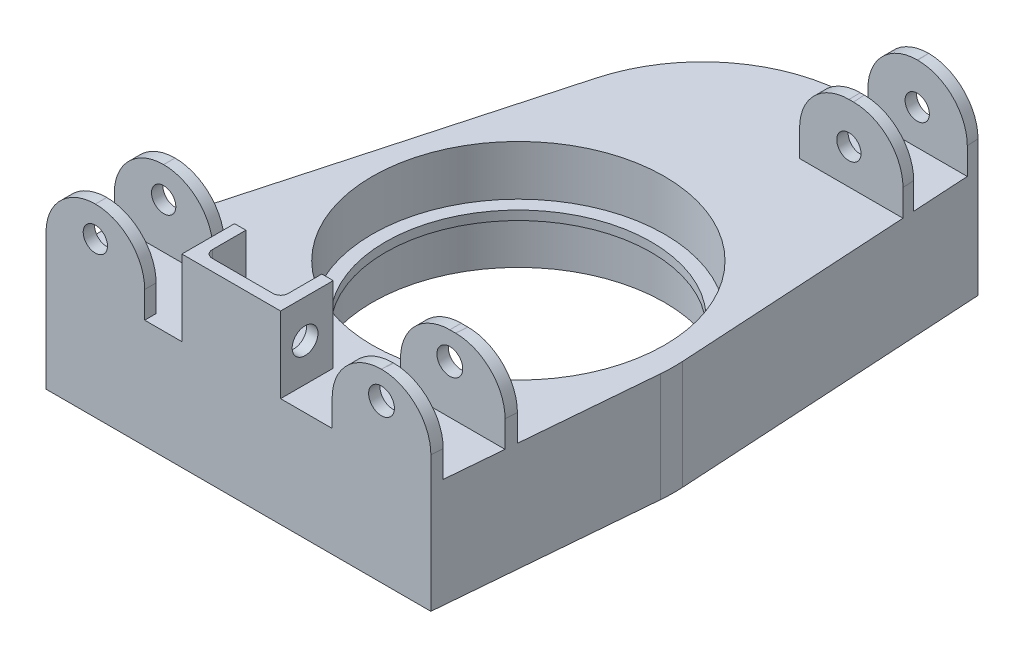
SolidWorks part; units mm, degrees
ref_plane "Front Plane" through (0, 0, 0) normal (0, 0, 1) x (1, 0, 0)
ref_plane "Top Plane" through (0, 0, 0) normal (0, 1, 0) x (1, 0, 0)
ref_plane "Right Plane" through (0, 0, 0) normal (1, 0, 0) x (0, 0, -1)
sketch "Sketch1" plane through (0, 0, 0) normal (0, 1, 0) x (1, 0, 0)
  line L0 (-78.3166, -79.7284) -> (50.4493, -79.7284)
  line L1 (56.8393, -5.2886) -> (50.4493, 103.3395)
  line L2 (50.4493, 103.3395) -> (9.0638, 103.3395)
  line L3 (-39.909, 66.0414) -> (-72.7449, -53.0584)
  line L4 (50.4493, 103.3395) -> (50.4493, -79.7284) construction
  line L5 (50.4493, -79.7284) -> (56.8393, -5.2886)
  line L6 (-78.3166, -79.7284) -> (-78.3166, -53.0584)
  line L7 (-78.3166, -53.0584) -> (-72.7449, -53.0584)
  circle A0 centre (0, 0) radius 48.895
  circle A2 centre (0, 0) radius 120.65
  arc A3 (9.0638, 103.3395) -> (-39.909, 66.0414) centre (9.0638, 52.5395) ccw
  point P10 (0, -48.895)
  point P11 (48.895, 0)
  point P16 (-48.895, 0)
  dimension "D2" = 97.79
  dimension "D3" = 7.62
  dimension "D4" = 8.89
  dimension "D5" = 26.67
  dimension "D1" = 241.3
  dimension "D6" = 50.8
extrude "Base" add sketch "Sketch1" along normal blind 36.5 contours L2 L3 L0 L1 A0 | L1 L4 A0 L5 region at (-76.0411, 0, 66.3934)
sketch "Sketch2" plane through (0, 36.5, 0) normal (0, 1, 0) x (1, 0, 0)
  line L0 (50.4493, 103.3395) -> (50.6734, 99.5295)
  line L1 (56.8393, -5.2886) -> (50.4493, 103.3395) construction
  line L2 (50.6734, 99.5295) -> (17.4293, 99.5295)
  line L3 (17.4293, 99.5295) -> (17.4293, 103.3395)
  line L4 (50.4493, 103.3395) -> (9.0638, 103.3395) construction
  line L5 (17.4293, 103.3395) -> (50.4493, 103.3395)
  line L6 (17.4293, -75.9184) -> (50.7764, -75.9184)
  line L7 (50.7764, -75.9184) -> (50.4493, -79.7284)
  line L8 (-78.3166, -79.7284) -> (50.4493, -79.7284) construction
  line L9 (50.4493, -79.7284) -> (17.4293, -79.7284)
  line L10 (17.4293, -79.7284) -> (17.4293, -75.9184)
  line L11 (17.4293, 103.3395) -> (17.4293, -79.7284) construction
  line L12 (50.4493, -79.7284) -> (56.8393, -5.2886) construction
  line L13 (17.4293, 80.4795) -> (17.4293, 76.6695)
  line L14 (17.4293, 76.6695) -> (52.0182, 76.6695)
  line L15 (52.0182, 76.6695) -> (51.794, 80.4795)
  line L16 (51.794, 80.4795) -> (17.4293, 80.4795)
  line L17 (-78.3166, -79.7284) -> (-78.3166, -53.0584) construction
  line L18 (17.4293, -53.0584) -> (52.7387, -53.0584)
  line L19 (17.4293, -53.0584) -> (17.4293, -56.8684)
  line L20 (17.4293, -56.8684) -> (52.4116, -56.8684)
  line L21 (52.7387, -53.0584) -> (52.4116, -56.8684)
  line L22 (-45.2966, -53.0584) -> (-78.3166, -53.0584)
  line L23 (-45.2966, -53.0584) -> (-45.2966, -56.8684)
  line L24 (-45.2966, -56.8684) -> (-78.3166, -56.8684)
  line L25 (-78.3166, -53.0584) -> (-78.3166, -56.8684)
  line L26 (-45.2966, -79.7284) -> (-45.2966, -60.0458) construction
  line L27 (-78.3166, -75.9184) -> (-45.2966, -75.9184)
  line L28 (-78.3166, -75.9184) -> (-78.3166, -79.7284)
  line L29 (-78.3166, -79.7284) -> (-45.2966, -79.7284)
  line L30 (-45.2966, -75.9184) -> (-45.2966, -79.7284)
  line L31 (-78.3166, -79.7284) -> (50.4493, -79.7284) construction
  dimension "D1" = 33.02
  dimension "D2" = 3.81
  dimension "D3" = 3.81
  dimension "D4" = 19.05
  dimension "D5" = 3.81
  dimension "D6" = 3.81
  dimension "D7" = 19.05
  dimension "D8" = 33.02
  dimension "D9" = 3.81
  dimension "D10" = 3.81
extrude "A-Arms" add sketch "Sketch2" along normal blind 25.4
fillet "Fillet a-arm tab f" radius 16.51 12 edges at (50.6128, 61.9, 77.8234) (52.5752, 61.9, 54.9634) (17.4293, 61.9, 77.8234) (17.4293, 61.9, 54.9634) (51.9061, 61.9, -78.5745) (50.5614, 61.9, -101.4345) (17.4293, 61.9, -78.5745) (17.4293, 61.9, -101.4345) (-78.3166, 61.9, 77.8234) (-45.2966, 61.9, 77.8234) (-45.2966, 61.9, 54.9634) (-78.3166, 61.9, 54.9634)
fillet "Fillet2" radius 50.8 1 edges at (56.8393, 18.25, 5.2886)
ref_plane "Plane1" through (0, 1, 0) normal (0, -1, 0) x (-1, 0, 0)
sketch "Sketch3" plane through (0, 1, 0) normal (0, -1, 0) x (-1, 0, 0)
  line L0 (43.8545, 51.7309) -> (51.7371, 53.9041)
  line L1 (39.909, 66.0414) -> (72.7449, -53.0584) construction
  line L2 (63.9719, -21.2377) -> (72.1885, -18.9724)
  line L3 (54.0145, 33.5988) -> (63.3923, -0.4157)
  line L4 (43.8545, 51.7309) -> (63.9719, -21.2377)
  circle A0 centre (0, 0) radius 71.12
  circle A1 centre (53.7624, 46.5582) radius 4.191
  circle A2 centre (70.1632, -11.6265) radius 4.191
  arc A3 (56.852, 39.5926) -> (51.7371, 53.9041) centre (53.7624, 46.5582) ccw
  arc A4 (72.1885, -18.9724) -> (69.039, -4.0899) centre (70.1632, -11.6265) ccw
  arc A5 (63.3923, -0.4157) -> (69.039, -4.0899) centre (68.2896, 0.9345) ccw
  arc A6 (54.0145, 33.5988) -> (56.852, 39.5926) centre (58.9118, 34.949) cw
  dimension "D1" = 60.452
  dimension "D2" = 142.24
  dimension "D3" = 8.382
  dimension "D4" = 8.382
  dimension "D5" = 15.24
  dimension "D6" = 15.24
  dimension "D7" = 5.08
extrude "Boss-Extrude3" add sketch "Sketch3" against normal blind 10 contours L3 A6 A3 A0 A1 L0 L4 L2 A2 A4 A5 | A0 A3 L0 A1 | L2 A4 A0 A2 region at (-57.0001, 1, -15.6865) region at (-49.7533, 1, -53.1565) region at (-69.0083, 1, 17.9571)
fillet "Fillet3" radius 12.7 2 edges at (-43.8545, 6, -51.7309) (-63.9719, 6, 21.2377)
sketch "Sketch6" plane through (0, 0, -103.3395) normal (0, 0, -1) x (-1, 0, 0)
  line L0 (-33.9251, 61.9) -> (-33.9251, 40.2979) construction
  circle A1 centre (-33.9251, 48.2) radius 4.064
  dimension "D1" = 13.7
  dimension "D2" = 8.128
extrude "Tab Holes 1" cut sketch "Sketch6" against normal blind 38.1
sketch "Sketch7" plane through (0, 0, 53.0584) normal (0, 0, -1) x (-1, 0, 0)
  line L0 (61.8066, 61.9) -> (61.8066, 41.58) construction
  circle A0 centre (61.8066, 51.74) radius 4.064
  dimension "D1" = 10.16
  dimension "D2" = 8.128
extrude "Tab Holes 2" cut sketch "Sketch7" against normal through all
ref_plane "midplane" through (0, 18.25, 0) normal (0, 1, 0) x (1, 0, 0)
sketch "Sketch8" plane through (0, 18.25, 0) normal (0, 1, 0) x (1, 0, 0)
  circle A0 centre (0, 0) radius 48.895
  circle A1 centre (0, 0) radius 44.45
extrude "mid-feature bearing" add sketch "Sketch8" along normal blind 1.524 and the other way blind 1.524
sketch "Sketch9" plane through (0, 36.5, 0) normal (0, 1, 0) x (1, 0, 0)
  line L0 (-45.2966, -79.7284) -> (17.4293, -79.7284) construction
  line L1 (-32.844, -79.7284) -> (0.176, -79.7284)
  line L2 (-32.844, -79.7284) -> (-32.844, -75.9184)
  line L3 (-32.844, -75.9184) -> (0.176, -75.9184)
  line L4 (0.176, -79.7284) -> (0.176, -75.9184)
  line L6 (0.176, -75.9184) -> (-3.634, -75.9184)
  line L7 (0.176, -75.9184) -> (0.176, -62.1226)
  line L8 (0.176, -62.1226) -> (-3.634, -62.1226)
  line L9 (-3.634, -75.9184) -> (-3.634, -62.1226)
  line L10 (-32.844, -75.9184) -> (-29.034, -75.9184)
  line L11 (-32.844, -75.9184) -> (-32.844, -62.1226)
  line L12 (-32.844, -62.1226) -> (-29.034, -62.1226)
  line L13 (-29.034, -75.9184) -> (-29.034, -62.1226)
  line M30 (-45.2966, -79.7284) -> (17.4293, -79.7284)
  dimension "D1" = 3.81
  dimension "D2" = 3.81
  dimension "D3" = 3.81
  dimension "D4" = 25.4
extrude "Boss-Extrude5" add sketch "Sketch9" along normal blind 25.4 contours L3 L13 L12 L11 | L4 L3 L2 M30 | L9 L3 L7 L8 region at (-16.334, 36.5, 77.8234) region at (-30.939, 36.5, 69.0205) region at (-1.729, 36.5, 69.0205)
fillet "Pushrod Str" radius 2.54 2 edges at (-3.634, 49.2, 75.9184) (-29.034, 49.2, 75.9184)
sketch "Sketch10" plane through (-32.844, 0, 0) normal (-1, 0, 0) x (0, 0, 1)
  line L0 (62.1226, 49.2) -> (80.5175, 49.2) construction
  line L1 (62.1226, 61.9) -> (62.1226, 36.5) construction
  circle A0 centre (71.5365, 49.2) radius 4.318
extrude "Pushrod Holes" cut sketch "Sketch10" against normal through all
mirror "Mirror2" [suppressed] of bodies 108
delete or keep bodies "Body-Delete/Keep 1" [suppressed] type delete bodies bodies 108
sketch "Sketch11" plane through (0, 0, 79.7284) normal (0, 0, -1) x (-1, 0, 0)
  line L0 (-33.9393, 61.9) -> (-33.9393, 36.5) construction
  line L2 (-17.4293, 36.5) -> (-50.4493, 36.5) construction
  line L3 (-50.4493, 45.39) -> (-50.4493, 0) construction
  circle A0 centre (-33.9393, 52.74) radius 4.318
  arc A1 (-17.4293, 45.39) -> (-33.909, 61.9) centre (-33.9393, 45.39) ccw construction
  dimension "D1" = 9.16
extrude "Tab Holes 3" cut sketch "Sketch11" along normal blind 50.8
ref_plane "Plane2" through (0, 0, -90.0045) normal (0, 0, -1) x (-1, 0, 0)
ref_axis "Axis1" through (33.9251, 48.2, -76.6695) along (0, 0, -1)
ref_point "top wishbont att pt"
ref_plane "Plane3" through (0, 0, 66.3934) normal (0, 0, -1) x (-1, 0, 0)
ref_axis "Axis2" through (33.9393, 52.74, 53.0584) along (0, 0, 1)
ref_point "Bottom Wish"
ref_axis "Axis3" through (-61.8066, 51.74, 56.8684) along (0, 0, -1)
ref_point "Anchor tierod"
